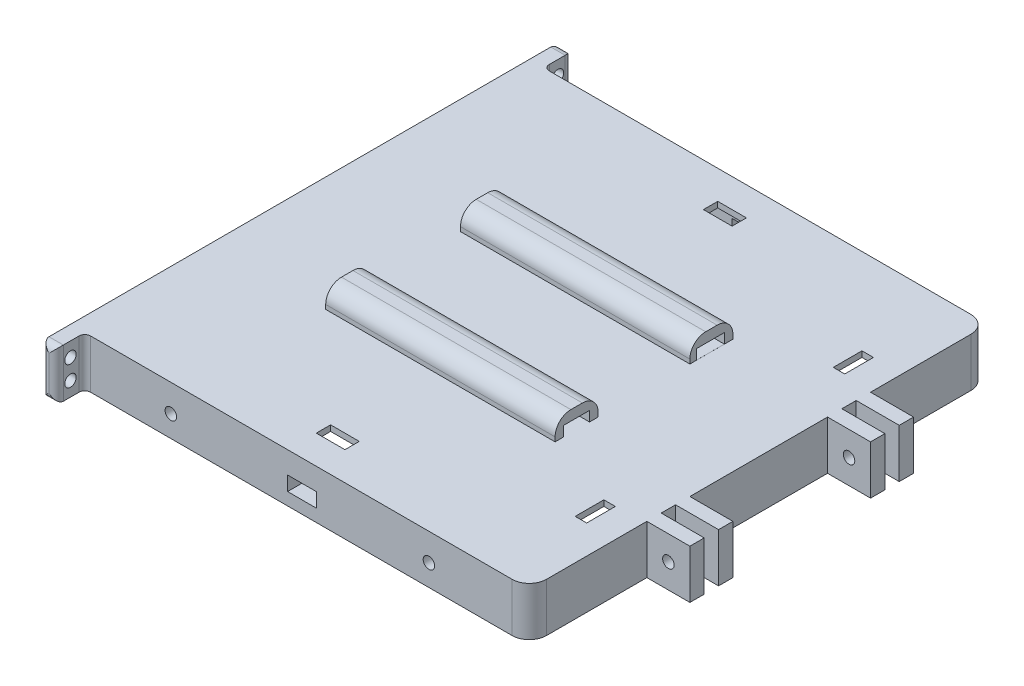
SolidWorks part; units mm, degrees
ref_plane "Front Plane" through (0, 0, 0) normal (0, 0, 1) x (1, 0, 0)
ref_plane "Top Plane" through (0, 0, 0) normal (0, 1, 0) x (1, 0, 0)
ref_plane "Right Plane" through (0, 0, 0) normal (1, 0, 0) x (0, 0, -1)
sketch "Sketch1" plane through (0, 0, 0) normal (0, 1, 0) x (1, 0, 0)
  line L1 (-188.9394, 182.7633) -> (192.0606, 182.7633)
  line L2 (-188.9394, 182.7633) -> (-188.9394, -198.2367)
  line L3 (-188.9394, -198.2367) -> (192.0606, -198.2367)
  line L4 (192.0606, 182.7633) -> (192.0606, -198.2367)
  line L5 (-201.6394, -210.9367) -> (204.7606, -210.9367)
  line L6 (-201.6394, -210.9367) -> (-201.6394, 195.4633)
  line L7 (-201.6394, 195.4633) -> (204.7606, 195.4633)
  line L8 (204.7606, -210.9367) -> (204.7606, 195.4633)
  point P4 (1.5606, -7.7367)
  dimension "D1" = 381
  dimension "D2" = 381
  dimension "D3" = 12.7
  dimension "D4" = 12.7
  dimension "D5" = 12.7
  dimension "D6" = 12.7
extrude "Boss-Extrude2" add sketch "Sketch1" along normal blind 38.1
sketch "Sketch2" plane through (0, 38.1, 0) normal (0, 1, 0) x (1, 0, 0)
  line L1 (-201.6394, 195.4633) -> (204.7606, 195.4633)
  line L2 (-201.6394, 195.4633) -> (-201.6394, -210.9367)
  line L3 (-201.6394, -210.9367) -> (204.7606, -210.9367)
  line L4 (204.7606, 195.4633) -> (204.7606, -210.9367)
extrude "Boss-Extrude3" add sketch "Sketch2" along normal blind 5.08
sketch "Sketch5" plane through (0, 0, 198.2367) normal (0, 0, -1) x (-1, 0, 0)
  line L0 (-204.7606, 43.18) -> (-204.7606, 0) construction
  line L1 (-115.8606, 8.5776) -> (-106.7912, 13.8138)
  line L2 (-106.7912, 13.8138) -> (-106.7912, 24.2862)
  line L3 (-106.7912, 24.2862) -> (-115.8606, 29.5224)
  line L4 (-115.8606, 29.5224) -> (-124.93, 24.2862)
  line L5 (-124.93, 24.2862) -> (-124.93, 13.8138)
  line L6 (-124.93, 13.8138) -> (-115.8606, 8.5776)
  line L7 (201.6394, 43.18) -> (201.6394, 0) construction
  line L8 (112.7394, 29.5224) -> (103.67, 24.2862)
  line L9 (103.67, 24.2862) -> (103.67, 13.8138)
  line L10 (103.67, 13.8138) -> (112.7394, 8.5776)
  line L11 (112.7394, 8.5776) -> (121.8088, 13.8138)
  line L12 (121.8088, 13.8138) -> (121.8088, 24.2862)
  line L13 (121.8088, 24.2862) -> (112.7394, 29.5224)
  circle A0 centre (-115.8606, 19.05) radius 9.0694 construction
  circle A1 centre (112.7394, 19.05) radius 9.0694 construction
  dimension "D1" = 88.9
  dimension "D2" = 88.9
extrude "Cut-Extrude3" cut sketch "Sketch5" against normal blind 5.08
sketch "Sketch6" plane through (0, 0, 198.2367) normal (0, 0, -1) x (-1, 0, 0)
  line L0 (201.6394, 43.18) -> (201.6394, 0) construction
  circle A0 centre (-115.8606, 19.05) radius 5.08
  circle A1 centre (112.7394, 19.05) radius 5.08
  dimension "D1" = 10.16
  dimension "D3" = 10.16
  dimension "D2" = 88.9
extrude "Cut-Extrude4" cut sketch "Sketch6" against normal through all both and the other way through all
sketch "Sketch7" plane through (0, 0, -182.7633) normal (0, 0, 1) x (1, 0, 0)
  line L1 (-112.7394, 29.5224) -> (-121.8088, 24.2862)
  line L2 (-121.8088, 24.2862) -> (-121.8088, 13.8138)
  line L3 (-121.8088, 13.8138) -> (-112.7394, 8.5776)
  line L4 (-112.7394, 8.5776) -> (-103.67, 13.8138)
  line L5 (-103.67, 13.8138) -> (-103.67, 24.2862)
  line L6 (-103.67, 24.2862) -> (-112.7394, 29.5224)
  line L7 (115.8606, 29.5224) -> (106.7912, 24.2862)
  line L8 (106.7912, 24.2862) -> (106.7912, 13.8138)
  line L9 (106.7912, 13.8138) -> (115.8606, 8.5776)
  line L10 (115.8606, 8.5776) -> (124.93, 13.8138)
  line L11 (124.93, 13.8138) -> (124.93, 24.2862)
  line L12 (124.93, 24.2862) -> (115.8606, 29.5224)
  circle A0 centre (-112.7394, 19.05) radius 9.0694 construction
  circle A1 centre (115.8606, 19.05) radius 9.0694 construction
extrude "Cut-Extrude6" cut sketch "Sketch7" against normal blind 5.08
sketch "Sketch8" plane through (-201.6394, 0, 0) normal (-1, 0, 0) x (0, 0, 1)
  line L0 (-195.4633, 43.18) -> (-195.4633, 0) construction
  line L1 (-220.8633, 43.18) -> (236.3367, 43.18)
  line L2 (-220.8633, 43.18) -> (-220.8633, 0)
  line L3 (-220.8633, 0) -> (236.3367, 0)
  line L4 (236.3367, 43.18) -> (236.3367, 0)
  line L5 (210.9367, 43.18) -> (210.9367, 0) construction
  dimension "D1" = 25.4
  dimension "D2" = 25.4
extrude "Boss-Extrude4" add sketch "Sketch8" against normal blind 12.7
sketch "Sketch9" plane through (-188.9394, 0, 0) normal (1, 0, 0) x (0, 0, -1)
  line L1 (-236.3367, 0) -> (-236.3367, 43.18) construction
  line L2 (-236.3367, 43.18) -> (-210.9367, 43.18) construction
  line L3 (-210.9367, 0) -> (-236.3367, 0) construction
  line L4 (220.8633, 43.18) -> (220.8633, 0) construction
  circle A0 centre (208.1633, 30.48) radius 5.08
  circle A1 centre (-223.6367, 30.48) radius 5.08
  circle A2 centre (-223.6367, 12.7) radius 5.08
  circle A3 centre (208.1633, 12.7) radius 5.08
  dimension "D1" = 10.16
  dimension "D2" = 10.16
  dimension "D4" = 12.7
  dimension "D5" = 12.7
  dimension "D6" = 12.7
  dimension "D3" = 12.7
extrude "Cut-Extrude7" cut sketch "Sketch9" against normal through all
fillet "Fillet2" radius 15.24 2 edges at (204.7606, 21.59, 210.9367) (204.7606, 21.59, -195.4633)
fillet "Fillet3" radius 5.08 2 edges at (-188.9394, 21.59, -195.4633) (-188.9394, 21.59, 210.9367)
fillet "Fillet4" radius 6.35 8 edges at (-195.2894, 43.18, 236.3367) (-188.9394, 21.59, 236.3367) (-195.2894, 0, 236.3367) (-201.6394, 21.59, 236.3367) (-195.2894, 0, -220.8633) (-188.9394, 21.59, -220.8633) (-195.2894, 43.18, -220.8633) (-201.6394, 21.59, -220.8633)
sketch "Sketch10" plane through (204.7606, 0, 0) normal (1, 0, 0) x (0, 0, -1)
  line L0 (214.5133, 0) -> (-229.9867, 0) construction
  line L1 (-134.7367, 12.7) -> (-109.3367, 12.7)
  line L2 (-134.7367, 12.7) -> (-134.7367, 22.86)
  line L3 (-134.7367, 22.86) -> (-109.3367, 22.86)
  line L4 (-109.3367, 12.7) -> (-109.3367, 22.86)
  line L5 (-236.3367, 6.35) -> (-236.3367, 36.83) construction
  line L6 (220.8633, 36.83) -> (220.8633, 6.35) construction
  line L7 (93.8633, 22.86) -> (119.2633, 22.86)
  line L8 (93.8633, 22.86) -> (93.8633, 12.7)
  line L9 (93.8633, 12.7) -> (119.2633, 12.7)
  line L10 (119.2633, 22.86) -> (119.2633, 12.7)
  dimension "D1" = 25.4
  dimension "D2" = 10.16
  dimension "D3" = 12.7
  dimension "D4" = 101.6
  dimension "D5" = 101.6
  dimension "D6" = 25.4
extrude "Cut-Extrude8" cut sketch "Sketch10" against normal through all both and the other way through all
sketch "Sketch11" plane through (0, 38.1, 0) normal (0, -1, 0) x (-1, 0, 0)
  line L0 (-192.0606, -198.2367) -> (-192.0606, 182.7633) construction
  line L1 (-179.3606, -134.7367) -> (-169.2006, -134.7367)
  line L2 (-179.3606, -134.7367) -> (-179.3606, -109.3367)
  line L3 (-179.3606, -109.3367) -> (-169.2006, -109.3367)
  line L4 (-169.2006, -134.7367) -> (-169.2006, -109.3367)
  line L5 (188.9394, 182.7633) -> (188.9394, -198.2367) construction
  line L6 (176.2394, -134.7367) -> (166.0794, -134.7367)
  line L7 (176.2394, -134.7367) -> (176.2394, -109.3367)
  line L8 (176.2394, -109.3367) -> (166.0794, -109.3367)
  line L9 (166.0794, -134.7367) -> (166.0794, -109.3367)
  line L11 (-179.3606, 93.8633) -> (-169.2006, 93.8633)
  line L12 (-179.3606, 93.8633) -> (-179.3606, 119.2633)
  line L13 (-179.3606, 119.2633) -> (-169.2006, 119.2633)
  line L14 (-169.2006, 93.8633) -> (-169.2006, 119.2633)
  line L15 (166.0794, 119.2633) -> (176.2394, 119.2633)
  line L16 (166.0794, 119.2633) -> (166.0794, 93.8633)
  line L17 (166.0794, 93.8633) -> (176.2394, 93.8633)
  line L18 (176.2394, 119.2633) -> (176.2394, 93.8633)
  dimension "D1" = 10.16
  dimension "D2" = 12.7
  dimension "D3" = 10.16
  dimension "D4" = 12.7
extrude "Cut-Extrude9" cut sketch "Sketch11" against normal through all both and the other way through all
sketch "Sketch13" plane through (204.7606, 0, 0) normal (1, 0, 0) x (0, 0, -1)
  line L0 (-195.6967, 43.18) -> (180.2233, 43.18) construction
  line L1 (-86.4767, 43.18) -> (-48.3767, 43.18)
  line L2 (-86.4767, 43.18) -> (-86.4767, 60.96)
  line L3 (-86.4767, 60.96) -> (-48.3767, 60.96)
  line L4 (-48.3767, 43.18) -> (-48.3767, 60.96)
  line L5 (-109.3367, 22.86) -> (-109.3367, 12.7) construction
  line L6 (32.9033, 43.18) -> (71.0033, 43.18)
  line L7 (32.9033, 43.18) -> (32.9033, 60.96)
  line L8 (32.9033, 60.96) -> (71.0033, 60.96)
  line L9 (71.0033, 43.18) -> (71.0033, 60.96)
  line L10 (93.8633, 12.7) -> (93.8633, 22.86) construction
  line L11 (-78.8567, 47.7383) -> (-78.8567, 43.18)
  line L13 (-78.8567, 47.7383) -> (-78.8567, 52.07)
  line L14 (-78.8567, 52.07) -> (-55.9967, 52.07)
  line L15 (-55.9967, 48.1215) -> (-55.9967, 52.07)
  line L16 (-78.8567, 43.18) -> (-55.9967, 43.18)
  line L17 (-55.9967, 43.18) -> (-55.9967, 48.1215)
  line L18 (38.5835, 47.7637) -> (38.5835, 43.2054)
  line L19 (38.5835, 47.7637) -> (38.5835, 52.07)
  line L20 (38.5835, 52.07) -> (63.4167, 52.07)
  line L21 (63.4167, 47.7637) -> (63.4167, 52.07)
  line L22 (38.5835, 43.2054) -> (63.4167, 43.2054)
  line L23 (63.4167, 43.2054) -> (63.4167, 47.7637)
  point P14 (-67.4267, 52.07)
  point P27 (-55.9967, 50.0958)
  line M28 (180.2233, 43.18) -> (-195.6967, 43.18)
  dimension "D1" = 17.78
  dimension "D2" = 17.78
  dimension "D3" = 22.86
  dimension "D4" = 22.86
  dimension "D5" = 38.1
  dimension "D6" = 38.1
  dimension "D7" = 7.62
  dimension "D8" = 5.6801
  dimension "D9" = 7.5866
  dimension "D10" = 7.62
  dimension "D11" = 8.89
  dimension "D12" = 8.89
extrude "Boss-Extrude6" add sketch "Sketch13" against normal through all contours L17 L4 L3 L2 L1 L11 L13 L14 L15 M28 | L9 L8 L7 L23 L22 L18 L19 L20 L21 M28 region at (204.7606, 53.975, 67.4267) region at (204.7606, 54.2037, -52.4122)
fillet "Fillet5" radius 13.97 4 edges at (1.5606, 60.96, 48.3767) (1.5606, 60.96, 86.4767) (1.5606, 60.96, -32.9033) (1.5606, 60.96, -71.0033)
sketch "Sketch14" plane through (-201.6394, 0, 0) normal (-1, 0, 0) x (0, 0, 1)
  line L1 (-71.0033, 43.18) -> (86.4767, 43.18)
  line L2 (-71.0033, 43.18) -> (-71.0033, 64.0096)
  line L3 (-71.0033, 64.0096) -> (86.4767, 64.0096)
  line L4 (86.4767, 43.18) -> (86.4767, 64.0096)
extrude "Cut-Extrude10" cut sketch "Sketch14" against normal blind 101.6 and the other way through all
sketch "Sketch17" plane through (204.7606, 0, 0) normal (1, 0, 0) x (0, 0, -1)
  line L1 (-86.4767, 43.18) -> (71.0033, 43.18)
  line L2 (-86.4767, 43.18) -> (-86.4767, 64.9603)
  line L3 (-86.4767, 64.9603) -> (71.0033, 64.9603)
  line L4 (71.0033, 43.18) -> (71.0033, 64.9603)
extrude "Cut-Extrude11" cut sketch "Sketch17" against normal blind 101.6
sketch "Sketch18" plane through (204.7606, 0, 0) normal (1, 0, 0) x (0, 0, -1)
  line L0 (180.2233, 0) -> (180.2233, 43.18) construction
  line L1 (-195.6967, 0) -> (180.2233, 0)
  line L2 (-195.6967, 0) -> (-195.6967, 43.18)
  line L3 (-195.6967, 43.18) -> (180.2233, 43.18)
  line L4 (180.2233, 0) -> (180.2233, 43.18)
extrude "Boss-Extrude7" add sketch "Sketch18" against normal up to vertex (12.7 mm away) up to point (192.0606, 0, 198.2367)
sketch "Sketch19" plane through (204.7606, 0, 0) normal (1, 0, 0) x (0, 0, -1)
  line L0 (-195.6967, 0) -> (180.2233, 0) construction
  line L1 (91.3233, 0) -> (78.6233, 0)
  line L2 (91.3233, 0) -> (91.3233, 43.18)
  line L3 (91.3233, 43.18) -> (78.6233, 43.18)
  line L4 (78.6233, 0) -> (78.6233, 43.18)
  line L5 (-195.6967, 43.18) -> (180.2233, 43.18) construction
  line L6 (180.2233, 0) -> (180.2233, 43.18) construction
  line L7 (-195.6967, 43.18) -> (-195.6967, 0) construction
  line L8 (-94.0967, 0) -> (-106.7967, 0)
  line L9 (-94.0967, 0) -> (-94.0967, 43.18)
  line L10 (-94.0967, 43.18) -> (-106.7967, 43.18)
  line L11 (-106.7967, 0) -> (-106.7967, 43.18)
  line L13 (65.9233, 0) -> (53.2233, 0)
  line L14 (65.9233, 0) -> (65.9233, 43.18)
  line L15 (65.9233, 43.18) -> (53.2233, 43.18)
  line L16 (53.2233, 0) -> (53.2233, 43.18)
  line L17 (-81.3967, 0) -> (-68.6967, 0)
  line L18 (-81.3967, 0) -> (-81.3967, 43.18)
  line L19 (-81.3967, 43.18) -> (-68.6967, 43.18)
  line L20 (-68.6967, 0) -> (-68.6967, 43.18)
  dimension "D1" = 12.7
  dimension "D2" = 88.9
  dimension "D3" = 12.7
  dimension "D4" = 88.9
  dimension "D5" = 12.7
  dimension "D6" = 12.7
  dimension "D7" = 12.7
  dimension "D8" = 12.7
extrude "Boss-Extrude8" add sketch "Sketch19" along normal blind 38.1
sketch "Sketch20" plane through (0, 0, 106.7967) normal (0, 0, 1) x (1, 0, 0)
  circle A0 centre (223.8106, 21.59) radius 5.08
  point P2 (223.8106, 21.59)
  dimension "D1" = 10.16
extrude "Cut-Extrude12" cut sketch "Sketch20" against normal through all
sketch "Sketch21" plane through (0, 38.1, 0) normal (0, -1, 0) x (1, 0, 0)
  line L1 (-181.9997, 165.2488) -> (-158.7874, 165.2488)
  line L2 (-181.9997, 165.2488) -> (-181.9997, -132.532)
  line L3 (-181.9997, -132.532) -> (-158.7874, -132.532)
  line L4 (-158.7874, 165.2488) -> (-158.7874, -132.532)
extrude "Boss-Extrude10" add sketch "Sketch21" against normal up to surface (5.08 mm away) up to face at (101.678, 43.18, 7.7367)
sketch "Sketch22" plane through (0, 0, -195.4633) normal (0, 0, -1) x (-1, 0, 0)
  line L5 (-16.0651, 11.0504) -> (9.3349, 11.0504)
  line L6 (-16.0651, 11.0504) -> (-16.0651, 23.7504)
  line L7 (-16.0651, 23.7504) -> (9.3349, 23.7504)
  line L8 (9.3349, 11.0504) -> (9.3349, 23.7504)
  dimension "D1" = 12.7
  dimension "D2" = 25.4
extrude "Cut-Extrude13" cut sketch "Sketch22" against normal through all
sketch "Sketch23" plane through (0, 38.1, 0) normal (0, -1, 0) x (-1, 0, 0)
  line L0 (188.9394, -198.2367) -> (-192.0606, -198.2367) construction
  line L1 (9.3349, -185.5367) -> (-16.0651, -185.5367)
  line L2 (9.3349, -185.5367) -> (9.3349, -172.8367)
  line L3 (9.3349, -172.8367) -> (-16.0651, -172.8367)
  line L4 (-16.0651, -185.5367) -> (-16.0651, -172.8367)
  line L5 (-192.0606, 182.7633) -> (188.9394, 182.7633) construction
  line L6 (9.3349, 170.0633) -> (-16.0651, 170.0633)
  line L7 (9.3349, 170.0633) -> (9.3349, 157.3633)
  line L8 (9.3349, 157.3633) -> (-16.0651, 157.3633)
  line L9 (-16.0651, 170.0633) -> (-16.0651, 157.3633)
  dimension "D1" = 12.7
  dimension "D2" = 12.7
  dimension "D3" = 12.7
  dimension "D4" = 12.7
extrude "Cut-Extrude14" cut sketch "Sketch23" against normal through all
